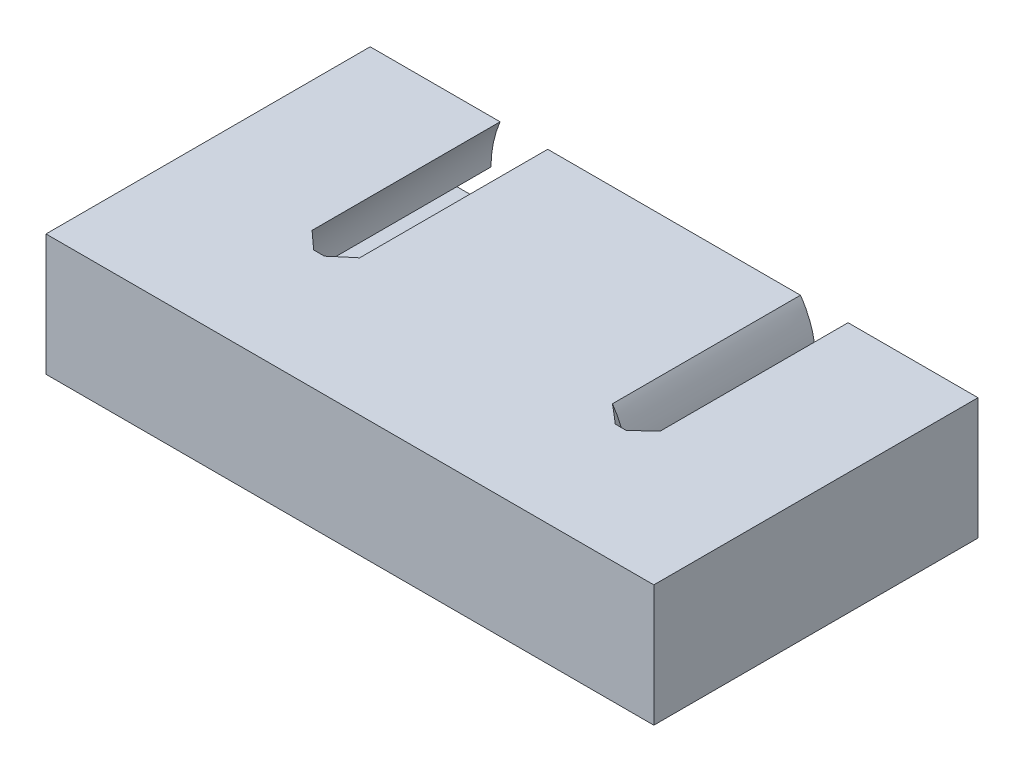
SolidWorks part; units mm, degrees
ref_plane "Front Plane" through (0, 0, 0) normal (0, 0, 1) x (1, 0, 0)
ref_plane "Top Plane" through (0, 0, 0) normal (0, 1, 0) x (1, 0, 0)
ref_plane "Right Plane" through (0, 0, 0) normal (1, 0, 0) x (0, 0, -1)
sketch "Sketch1" plane through (0, 0, 0) normal (0, 1, 0) x (1, 0, 0)
  line L0 (-27.5, 10) -> (-27.5, -5) construction
  line L1 (37.5, -20) -> (-37.5, -20)
  line L2 (37.5, -20) -> (37.5, 20)
  line L3 (37.5, 20) -> (-37.5, 20)
  line L4 (-37.5, -20) -> (-37.5, 20)
  line L5 (37.5, -20) -> (-37.5, 20) construction
  line L6 (37.5, 20) -> (-37.5, -20) construction
  line L7 (-27.5, -5) -> (-12.5, -5) construction
  point P0 (0, 0)
  dimension "D1" = 10
  dimension "D2" = 15
extrude "Boss-Extrude1" add sketch "Sketch1" along normal blind 7.5 and the other way blind 7.5
sketch "Sketch2" plane through (0, 0, 0) normal (0, 0, 1) x (1, 0, 0)
  line L0 (0, 14.7103) -> (0, -11.8256) construction
  line L135 (6.879, 18.7651) -> (-6.879, 18.7651)
  line L195 (-22.5996, 2.1) -> (-27.6, 2.1)
  line L196 (-27.6, 2.1) -> (-27.6, -2.1)
  line L197 (-27.6, -2.1) -> (-21.5, -2.1)
  line L198 (-21.5, -2.1) -> (-18.5, -2.1)
  line L210 (-18.5, -2.1) -> (-12.4, -2.1)
  line L211 (-12.4, -2.1) -> (-12.4, 2.1)
  line L212 (-12.4, 2.1) -> (-17.3994, 2.1)
  line L213 (27.6, 2.1) -> (22.5996, 2.1)
  line L214 (27.6, -2.1) -> (27.6, 2.1)
  line L215 (21.5, -2.1) -> (27.6, -2.1)
  line L216 (18.5, -2.1) -> (21.5, -2.1)
  line L217 (17.3994, 2.1) -> (12.4, 2.1)
  line L218 (12.4, 2.1) -> (12.4, -2.1)
  line L219 (12.4, -2.1) -> (18.5, -2.1)
  line L225 (-22.5996, 2.1) -> (-27.6, 2.1)
  line L226 (-27.6, 2.1) -> (-27.6, -2.1)
  line L227 (-27.6, -2.1) -> (-21.5, -2.1)
  line L228 (-21.5, -2.1) -> (-18.5, -2.1)
  line L229 (-18.5, -2.1) -> (-12.4, -2.1)
  line L230 (-12.4, -2.1) -> (-12.4, 2.1)
  line L231 (-12.4, 2.1) -> (-17.3994, 2.1)
  line L232 (27.6, 2.1) -> (22.5996, 2.1)
  line L233 (27.6, -2.1) -> (27.6, 2.1)
  line L234 (21.5, -2.1) -> (27.6, -2.1)
  line L235 (18.5, -2.1) -> (21.5, -2.1)
  line L236 (17.3994, 2.1) -> (12.4, 2.1)
  line L237 (12.4, 2.1) -> (12.4, -2.1)
  line L238 (12.4, -2.1) -> (18.5, -2.1)
  spline S0 degree 3 poles (-3220.6374, -2325.921) (373.8591, -188.5309) (52.6321, 53.1094) (-15.1049, 15.2212) (-16.8066, 13.9111) (-19.6086, 10.9436) (-20.7084, 9.2867) (-47.5716, -53.8552) (364.1538, -229.0171) (2057.8791, 3384.8063) knots -8.322497 -8.322497 -8.322497 -8.322497 0.25 0.25 0.5 0.5 0.75 0.75 9.520603 9.520603 9.520603 9.520603 only from (-6.879, 18.7651) to (-22.5996, 2.1)
  spline S1 degree 3 poles (-2057.8273, 3384.6957) (-364.1454, -229.0135) (47.5714, -53.8545) (20.7084, 9.2867) (19.6086, 10.9436) (16.8066, 13.9111) (15.1049, 15.2212) (-52.6325, 53.1096) (-373.8627, -188.5337) (3220.6983, -2325.9572) knots -8.520513 -8.520513 -8.520513 -8.520513 0.25 0.25 0.5 0.5 0.75 0.75 9.322546 9.322546 9.322546 9.322546 only from (22.5996, 2.1) to (6.879, 18.7651)
  spline S2 degree 3 poles (2198.0589, 3302.6669) (347.3904, -210.0974) (-43.9711, -40.5467) (-15.6024, 7.5459) (-15.0617, 8.259) (-13.7957, 9.5977) (-13.0704, 10.2233) (-10.6585, 11.9322) (-8.7336, 12.8451) (-4.5384, 14.0793) (-2.2696, 14.4) (2.2696, 14.4) (4.5384, 14.0793) (8.7336, 12.8451) (10.6585, 11.9322) (13.0704, 10.2233) (13.7957, 9.5977) (15.0617, 8.259) (15.6024, 7.5459) (43.9712, -40.5468) (-347.3927, -210.0984) (-2198.0753, 3302.6979) knots -3.856931 -3.856931 -3.856931 -3.856931 0.125 0.125 0.1875 0.1875 0.25 0.25 0.375 0.375 0.5 0.5 0.625 0.625 0.75 0.75 0.8125 0.8125 0.875 0.875 4.856943 4.856943 4.856943 4.856943 only from (-17.3994, 2.1) to (17.3994, 2.1)
  spline S3 degree 3 poles (-6.879, 18.7651) (-9.1294, 18.2052) (-11.2661, 17.3684) (-15.1049, 15.2212) (-16.8066, 13.9111) (-19.6086, 10.9436) (-20.7084, 9.2867) (-22.1974, 5.7868) (-22.5862, 3.9444) (-22.5996, 2.1) knots 0 0 0 0 0.25 0.25 0.5 0.5 0.75 0.75 1 1 1 1
  spline S4 degree 3 poles (22.5996, 2.1) (22.5862, 3.9444) (22.1974, 5.7868) (20.7084, 9.2867) (19.6086, 10.9436) (16.8066, 13.9111) (15.1049, 15.2212) (11.2661, 17.3684) (9.1294, 18.2052) (6.879, 18.7651) knots 0 0 0 0 0.25 0.25 0.5 0.5 0.75 0.75 1 1 1 1
  spline S5 degree 3 poles (-17.3994, 2.1) (-17.3812, 3.7095) (-16.9176, 5.3163) (-15.6024, 7.5459) (-15.0617, 8.259) (-13.7957, 9.5977) (-13.0704, 10.2233) (-10.6585, 11.9322) (-8.7336, 12.8451) (-4.5384, 14.0793) (-2.2696, 14.4) (2.2696, 14.4) (4.5384, 14.0793) (8.7336, 12.8451) (10.6585, 11.9322) (13.0704, 10.2233) (13.7957, 9.5977) (15.0617, 8.259) (15.6024, 7.5459) (16.9176, 5.3163) (17.3812, 3.7095) (17.3994, 2.1) knots 0 0 0 0 0.125 0.125 0.1875 0.1875 0.25 0.25 0.375 0.375 0.5 0.5 0.625 0.625 0.75 0.75 0.8125 0.8125 0.875 0.875 1 1 1 1
  dimension "D1" = 0.1
extrude "Cut-Extrude1" cut sketch "Sketch2" against normal blind 20 and the other way blind 5.2
chamfer "Chamfer1" distance 2 angle 45 4 edges
sketch "Sketch3" plane through (0, 0, -20) normal (0, 0, -1) x (-1, 0, 0)
  line L0 (0, 20.7181) -> (0, -22.0225) construction
  line L1 (-20, -2.1) -> (-20, -4.8) construction
  line L2 (-12.4, -2.1) -> (-27.6, -2.1) construction
  line L3 (-20, -4.8) -> (-20, -7.5) construction
  line L4 (-37.5, -7.5) -> (37.5, -7.5) construction
  circle A0 centre (-20, -4.8) radius 2
  circle A1 centre (20, -4.8) radius 2
  dimension "D1" = 4
extrude "Cut-Extrude2" cut sketch "Sketch3" against normal blind 9
sketch "Sketch4" plane through (0, -2.1, 0) normal (0, 1, 0) x (1, 0, 0)
  line L0 (0, 5.637) -> (0, -11.2367) construction
  line L1 (-20, 7.5) -> (-20, 11) construction
  line L3 (-18, 11) -> (-22, 11) construction
  line L4 (-22, 7.5) -> (-22, 10)
  line L5 (-22, 10) -> (-18, 10)
  line L6 (-18, 10) -> (-18, 7.5)
  line L7 (20, 7.5) -> (20, 11) construction
  line L8 (18, 10) -> (18, 7.5)
  line L9 (22, 10) -> (18, 10)
  line L10 (22, 7.5) -> (22, 10)
  line L11 (51.424, 10) -> (36.6389, 10) construction
  arc A0 (-22, 7.5) -> (-18, 7.5) centre (-20, 7.5) ccw
  arc A1 (22, 7.5) -> (18, 7.5) centre (20, 7.5) cw
  point P1 (-17.8497, 2.9966)
  point P18 (20, 1.852)
  point P21 (20, 6.4697)
  dimension "D1" = 4
  dimension "D2" = 3.5
extrude "Cut-Extrude3" cut sketch "Sketch4" against normal blind 4.7
fillet "Fillet1" radius 2 6 edges at (-22, -6.8, -8.75) (-18, -6.8, -8.75) (-20, -6.8, -5.5) (18, -6.8, -8.75) (22, -6.8, -8.75) (20, -6.8, -5.5)
